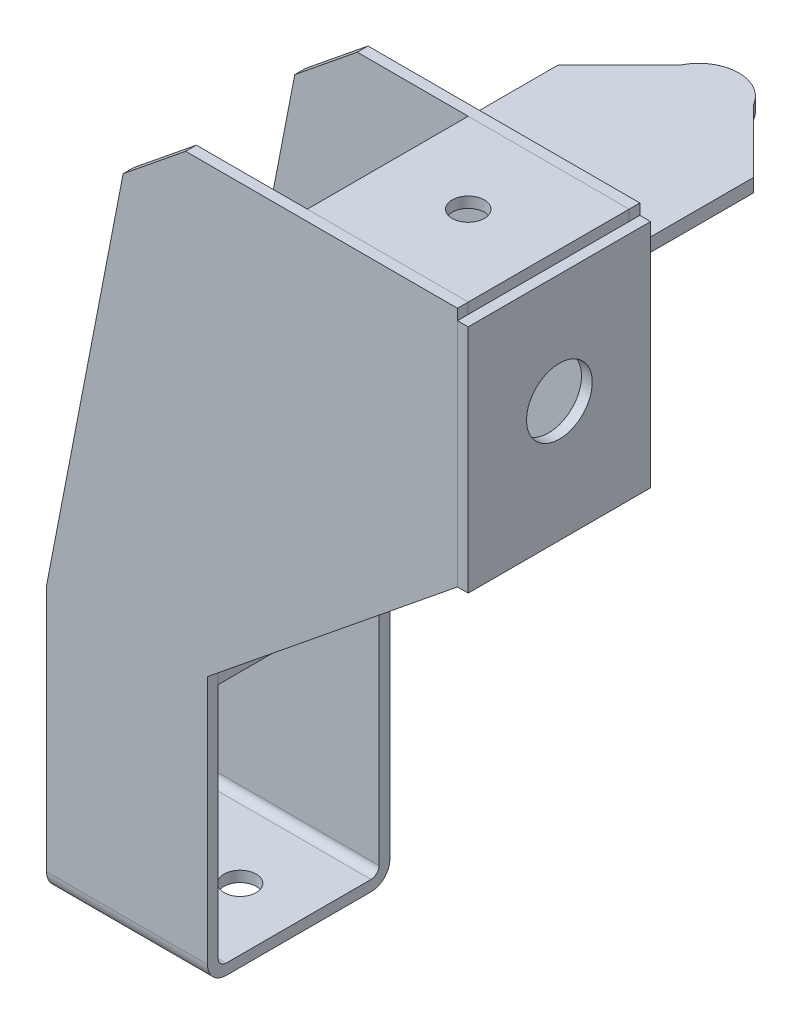
SolidWorks part; units mm, degrees
ref_plane "Front Plane" through (0, 0, 0) normal (0, 0, 1) x (1, 0, 0)
ref_plane "Top Plane" through (0, 0, 0) normal (0, 1, 0) x (1, 0, 0)
ref_plane "Right Plane" through (0, 0, 0) normal (1, 0, 0) x (0, 0, -1)
sketch "Sketch1" plane through (0, 0, 0) normal (0, 0, 1) x (1, 0, 0)
  line L0 (0, 0) -> (0, -100)
  line L1 (0, -2.2) -> (0, 2.2) construction
  line L2 (0, 0) -> (93.2275, 75.5556)
  line L3 (93.2275, 75.5556) -> (93.2275, 165.5556)
  line L4 (0, -100) -> (-60, -100)
  line L5 (-60, -100) -> (-60, -0.5906)
  line L6 (-60, -0.5906) -> (-31.4466, 146.6667)
  line L7 (-31.4466, 146.6667) -> (-8.1397, 165.5556)
  line L8 (-8.1397, 165.5556) -> (93.2275, 165.5556)
  point P0 (0, 0)
  dimension "D1" = 100
  dimension "D2" = 120
  dimension "D3" = 90
  dimension "D4" = 60
  dimension "D5" = 90
  dimension "D6" = 30
  dimension "D7" = 150
  dimension "D8" = 150
  dimension "D9" = 190
  dimension "D10" = 101.3672
  dimension "D11" = 129.023
  dimension "D12" = 99.4094
sketch "Sketch3" plane through (0, 0, 0) normal (1, 0, 0) x (0, 0, -1)
  line L2 (93.1124, 165.5556) -> (89.1124, 165.5556)
  line L3 (89.1124, 165.5556) -> (89.1124, -93)
  line L4 (86.1124, -96) -> (32.1124, -96)
  line L5 (0, 146.6667) -> (0, 165.5556) construction
  line L6 (0, 75.5556) -> (0, 165.5556) construction
  line L7 (0, -100) -> (0, -0.5906) construction
  line L8 (0, 84.2751) -> (0, -84.2751) construction
  line L9 (29.1124, -93) -> (29.1124, 165.5556)
  line L10 (29.1124, 165.5556) -> (25.1124, 165.5556)
  line L12 (93.1124, 161.5556) -> (93.1124, 161.5556)
  line L13 (93.1124, 165.5556) -> (93.1124, -93)
  line L14 (86.1124, -100) -> (32.1124, -100)
  line L15 (25.1124, -93) -> (25.1124, 168.1451)
  line L16 (25.1124, 161.5556) -> (25.1124, 161.5556)
  line L17 (93.1124, 161.5556) -> (93.1124, -93) construction
  line L18 (25.1124, -93) -> (25.1124, 161.5556) construction
  arc A0 (32.1124, -96) -> (29.1124, -93) centre (32.1124, -93) cw
  arc A1 (89.1124, -93) -> (86.1124, -96) centre (86.1124, -93) cw
  arc A2 (93.1124, -93) -> (86.1124, -100) centre (86.1124, -93) cw
  arc A3 (32.1124, -100) -> (25.1124, -93) centre (32.1124, -93) cw
  point P2 (0, 165.5556)
  point P7 (0, -100)
  point P20 (29.1124, -96)
  point P23 (89.1124, -96)
  dimension "D6" = 3
  dimension "D1" = 4
  dimension "D5" = 60
extrude "Boss-Extrude2" add sketch "Sketch3" along normal mid plane 214 contours A3 L14 A2 L13 L2 L3 A1 L4 A0 L9 L10 L15 region at (0, 36.2778, -90.3712)
sketch "Sketch4" plane through (0, 0, 0) normal (0, 0, 1) x (1, 0, 0)
  line L8 (-190, 11.8967) -> (-190, -230)
  line L9 (-190, -230) -> (130, -230)
  line L10 (130, -230) -> (130, -61.9751)
  line L11 (130, -61.9751) -> (223.2275, 13.5805)
  line L12 (223.2275, 13.5805) -> (223.2275, 295.5556)
  line L13 (223.2275, 295.5556) -> (-54.2043, 295.5556)
  line L14 (-54.2043, 295.5556) -> (-150.0618, 217.8685)
  line L15 (-150.0618, 217.8685) -> (-190, 11.8967)
  line L16 (-60, -0.5906) -> (-60, -100)
  line L17 (-60, -100) -> (0, -100)
  line L18 (0, -100) -> (0, 0)
  line L19 (0, 0) -> (93.2275, 75.5556)
  line L20 (93.2275, 75.5556) -> (93.2275, 165.5556)
  line L21 (93.2275, 165.5556) -> (-8.1397, 165.5556)
  line L22 (-8.1397, 165.5556) -> (-31.4466, 146.6667)
  line L23 (-31.4466, 146.6667) -> (-60, -0.5906)
  line L24 (-60, -0.5906) -> (-60, -100)
  line L25 (-60, -100) -> (0, -100)
  line L26 (0, -100) -> (0, 0)
  line L27 (0, 0) -> (93.2275, 75.5556)
  line L28 (93.2275, 75.5556) -> (93.2275, 165.5556)
  line L29 (93.2275, 165.5556) -> (-8.1397, 165.5556)
  line L30 (-8.1397, 165.5556) -> (-31.4466, 146.6667)
  line L31 (-31.4466, 146.6667) -> (-60, -0.5906)
  dimension "D1" = 0
  dimension "D2" = 130
extrude "Cut-Extrude1" cut sketch "Sketch4" against normal blind 214
sketch "Sketch5" plane through (0, 0, 0) normal (1, 0, 0) x (0, 0, -1)
  line L0 (89.1124, 0) -> (89.1124, -93) construction
  line L1 (29.1124, -0.5906) -> (89.1124, -0.5906)
  line L2 (29.1124, -0.5906) -> (29.1124, -4.5906)
  line L3 (29.1124, -4.5906) -> (89.1124, -4.5906)
  line L4 (89.1124, -0.5906) -> (89.1124, -4.5906)
  dimension "D1" = 4
  dimension "D2" = 60
extrude "Boss-Extrude3" add sketch "Sketch5" against normal blind 60 separate body
sketch "Sketch6" plane through (93.2275, 0, 0) normal (1, 0, 0) x (0, 0, -1)
  line L0 (89.1124, 165.5556) -> (89.1124, 75.5556) construction
  line L1 (29.1124, 165.5556) -> (89.1124, 165.5556)
  line L2 (29.1124, 165.5556) -> (29.1124, 161.5556)
  line L3 (29.1124, 161.5556) -> (89.1124, 161.5556)
  line L4 (89.1124, 165.5556) -> (89.1124, 161.5556)
  dimension "D1" = 4
extrude "Boss-Extrude4" add sketch "Sketch6" against normal blind 60 separate body
sketch "Sketch7" plane through (93.2275, 0, 0) normal (1, 0, 0) x (0, 0, -1)
  line L0 (25.1124, 161.5556) -> (93.1124, 161.5556)
  line L2 (25.1124, 161.5556) -> (25.1124, 75.5556)
  line L3 (25.1124, 75.5556) -> (93.1124, 75.5556)
  line L4 (93.1124, 161.5556) -> (93.1124, 75.5556)
extrude "Boss-Extrude5" add sketch "Sketch7" along normal blind 4 separate body
sketch "Sketch8" plane through (0, 0, -93.1124) normal (0, 0, -1) x (-1, 0, 0)
  line L1 (12.1021, 115) -> (-60.6218, 115)
  line L2 (12.1021, 115) -> (12.1021, 120)
  line L3 (12.1021, 120) -> (-60.6218, 120)
  line L4 (-60.6218, 115) -> (-60.6218, 120)
  line L5 (12.1021, 117.5) -> (37.1021, 117.5)
  line L7 (60, -0.5906) -> (31.4466, 146.6667) construction
  point P8 (60, -0.5906)
  dimension "D1" = 5
  dimension "D2" = 115
  dimension "D3" = 130
  dimension "D4" = 167.0653
  dimension "D5" = 115.635
  dimension "D6" = 25
extrude "Boss-Extrude6" add sketch "Sketch8" along normal blind 100 separate body contours L4 L1 L2 L3 region at (24.2599, 117.5, -93.1124)
chamfer "Chamfer1" distance 25 angle 45 1 edges at (-12.1021, 117.5, -193.1124)
chamfer "Chamfer2" distance 25 angle 45 1 edges at (60.6218, 117.5, -193.1124)
sketch "Sketch9" plane through (0, 115, 0) normal (0, -1, 0) x (1, 0, 0)
  line L2 (93.2275, -93.1124) -> (0, -93.1124) construction
  line L3 (60.6218, -168.1124) -> (60.6218, -93.1124) construction
  circle A1 centre (24.1218, -184.1124) radius 15
  dimension "D1" = 30
  dimension "D3" = 36.5
  dimension "D2" = 91
extrude "Boss-Extrude7" add sketch "Sketch9" against normal blind 5
sketch "Sketch10" plane through (97.2275, 0, 0) normal (1, 0, 0) x (0, 0, -1)
  line L0 (25.1124, 165.5556) -> (93.1124, 75.5556)
  circle A0 centre (59.1124, 120.5556) radius 12.25
  dimension "D1" = 24.5
extrude "Cut-Extrude2" cut sketch "Sketch10" against normal blind 4 contours L0 A0 | L0 A0 region at (97.2275, 123.6897, -63.2605) region at (97.2275, 117.4214, -54.9642)
sketch "Sketch12" plane through (0, 165.5556, 0) normal (0, 1, 0) x (1, 0, 0)
  line L0 (33.2275, 89.1124) -> (93.2275, 29.1124)
  circle A0 centre (63.2275, 59.1124) radius 6
  dimension "D1" = 12
extrude "Cut-Extrude5" cut sketch "Sketch12" against normal blind 8 contours L0 A0 | L0 A0 region at (65.0281, 165.5556, -60.913) region at (61.4268, 165.5556, -57.3118)
sketch "Sketch13" plane through (0, -100, 0) normal (0, -1, 0) x (1, 0, 0)
  circle A0 centre (-23.1606, -60.4397) radius 6
extrude "Cut-Extrude6" cut sketch "Sketch13" against normal blind 10
